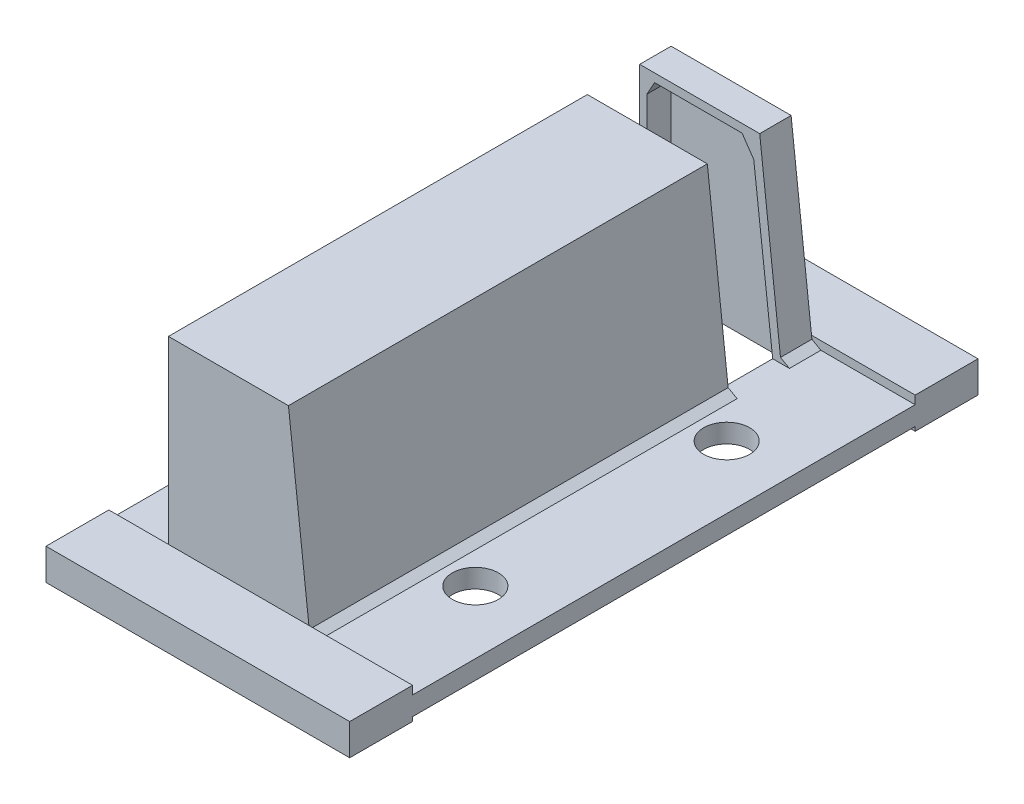
SolidWorks part; units mm, degrees
ref_plane "Front Plane" through (0, 0, 0) normal (0, 0, 1) x (1, 0, 0)
ref_plane "Top Plane" through (0, 0, 0) normal (0, 1, 0) x (1, 0, 0)
ref_plane "Right Plane" through (0, 0, 0) normal (1, 0, 0) x (0, 0, -1)
sketch "Sketch2" plane through (0, 0, 0) normal (0, 1, 0) x (1, 0, 0)
  line L0 (0, 38.1) -> (36.83, 38.1) construction
  line L1 (0, 0) -> (36.83, 0)
  line L2 (0, 0) -> (0, 76.2)
  line L3 (0, 76.2) -> (36.83, 76.2)
  line L4 (36.83, 0) -> (36.83, 76.2)
  line L5 (29.21, 38.1) -> (29.21, 53.34) construction
  line L6 (29.21, 38.1) -> (29.21, 22.86) construction
  line L7 (36.83, 68.58) -> (0, 68.58)
  line L15 (36.83, 7.62) -> (0, 7.62)
  line L16 (20.32, 7.62) -> (20.32, 68.58) construction
  line L19 (7.62, 68.58) -> (6.87, 68.58)
  line L21 (7.62, 7.62) -> (6.87, 7.62)
  circle A0 centre (29.21, 53.34) radius 2.794
  circle A1 centre (29.21, 22.86) radius 2.794
  dimension "D1" = 29.21
  dimension "D2" = 20.32
  dimension "D3" = 15.24
  dimension "D4" = 15.24
  dimension "D5" = 36.83
  dimension "D6" = 76.2
extrude "Boss-Extrude2" add sketch "Sketch2" along normal blind 3.81 contours L4 L15 L2 L1 | L7 L4 L3 L2 region at (18.415, 0, -3.81) region at (18.415, 0, -72.39)
extrude "Boss-Extrude3" add sketch "Sketch2<3>" along normal blind 2.286 from offset 0.508
sketch "Sketch2<3>" plane through (0, 0, 0) normal (0, 1, 0) x (1, 0, 0) same geometry as "Sketch2"
sketch "Sketch13" plane through (0, 0, -68.58) normal (0, 0, 1) x (1, 0, 0)
  line L0 (8.121, 2.794) -> (8.121, 24.638)
  line L1 (0, 2.794) -> (36.83, 2.794) construction
  line L2 (8.121, 2.794) -> (23.361, 2.794)
  line L3 (23.361, 2.794) -> (20.821, 24.638)
  line L4 (20.821, 24.638) -> (8.121, 24.638)
  line L5 (7.232, 2.794) -> (7.232, 25.654)
  line L6 (7.232, 25.654) -> (21.7842, 25.654)
  line L7 (21.7842, 25.654) -> (24.377, 2.794)
  line L8 (8.121, 2.794) -> (7.232, 2.794)
  line L9 (23.361, 2.794) -> (24.377, 2.794)
  line L10 (9.0465, 24.638) -> (8.121, 22.9754)
  line L11 (19.6493, 24.638) -> (21.06, 22.582)
  line L12 (7.232, 3.2985) -> (6.216, 2.794)
  line L13 (6.216, 2.794) -> (7.232, 2.794)
  line L14 (24.377, 2.794) -> (25.393, 2.794)
  line L15 (25.393, 2.794) -> (24.307, 3.4106)
  line M2 (0, 2.794) -> (36.83, 2.794)
  line M4 (36.83, 3.81) -> (0, 3.81)
  dimension "D1" = 15.24
  dimension "D3" = 1.016
  dimension "D4" = 22.86
  dimension "D5" = 0.889
extrude "Boss-Extrude11" add sketch "Sketch13" along normal blind 3.81 contours L5 L12 M2 | L5 L0 M2 M4 | L7 L6 L5 L0 L4 L3 M4 | L10 L4 L0 | L4 L11 L3 | L7 L3 M4 M2 | L15 L7 M2 region at (7.844, 13.3927, -68.58) region at (8.4295, 24.0838, -68.58) region at (7.6765, 3.302, -68.58) region at (23.8106, 3.3022, -68.58) region at (20.5101, 23.9527, -68.58) region at (6.8933, 2.9622, -68.58) region at (24.6923, 2.9995, -68.58)
extrude "Boss-Extrude12" add sketch "Sketch13<3>" along normal blind 0.889 contours L11 L4 L10 L0 L3 M4 | L3 L0 M2 M4 region at (15.0892, 13.8527, -68.58) region at (15.7115, 3.3013, -68.58)
sketch "Sketch13<3>" plane through (0, 0, -68.58) normal (0, 0, 1) x (1, 0, 0) same geometry as "Sketch13"
extrude "Boss-Extrude14" add sketch "Sketch13<6>" along direction (0, 0, 1) on the side of the normal blind 50.8 from offset 10.16 contours L15 L7 M2 | L7 L3 M4 M2 | L5 L0 M2 M4 | L5 L12 M2 | L7 L6 L5 L0 L4 L3 M4 | L4 L11 L3 | L10 L4 L0 region at (7.844, 13.3927, -68.58) region at (8.4295, 24.0838, -68.58) region at (7.6765, 3.302, -68.58) region at (23.8106, 3.3022, -68.58) region at (20.5101, 23.9527, -68.58) region at (6.8933, 2.9622, -68.58) region at (24.6923, 2.9995, -68.58)
sketch "Sketch13<6>" plane through (0, 0, -68.58) normal (0, 0, 1) x (1, 0, 0) same geometry as "Sketch13"
extrude "Boss-Extrude17" add sketch "Sketch13<7>" along normal up to surface (60.96 mm away) from offset 60.071 contours L11 L4 L10 L0 L3 M4 | L3 L0 M2 M4 region at (15.0892, 13.8527, -68.58) region at (15.7115, 3.3013, -68.58) up to face at (14.9751, 16.1381, -7.62)
sketch "Sketch13<7>" plane through (0, 0, -68.58) normal (0, 0, 1) x (1, 0, 0) same geometry as "Sketch13"
sketch "Sketch14" plane through (0, 2.794, 0) normal (0, 1, 0) x (1, 0, 0)
  line L1 (23.361, 67.691) -> (8.121, 67.691)
  line L2 (23.361, 67.691) -> (23.361, 8.509)
  line L3 (23.361, 8.509) -> (8.121, 8.509)
  line L4 (8.121, 67.691) -> (8.121, 8.509)
extrude "Cut-Extrude3" cut sketch "Sketch14" against normal through all contours L2 L3 L4 L1
